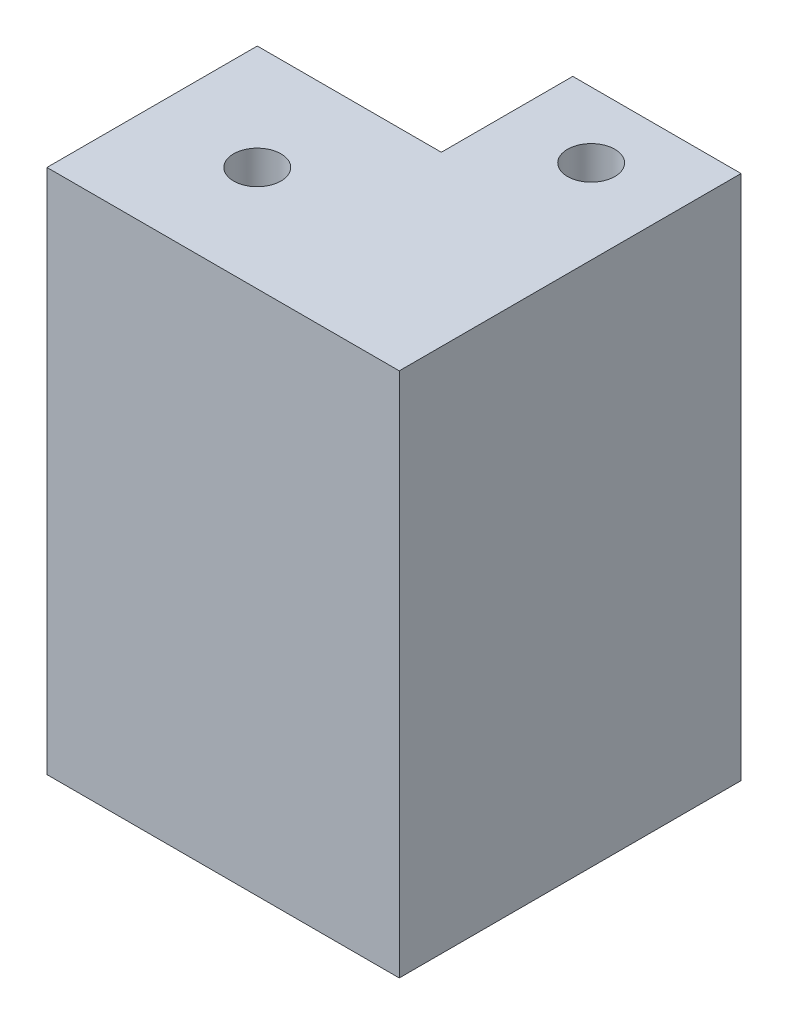
SolidWorks part; units mm, degrees
ref_plane "Front Plane" through (0, 0, 0) normal (0, 0, 1) x (1, 0, 0)
ref_plane "Top Plane" through (0, 0, 0) normal (0, 1, 0) x (1, 0, 0)
ref_plane "Right Plane" through (0, 0, 0) normal (1, 0, 0) x (0, 0, -1)
sketch "Sketch1" plane through (0, 0, 0) normal (0, 1, 0) x (1, 0, 0)
  line L19 (0, -40) -> (0, 0) construction
  line L24 (-25, 0) -> (-5, -40) construction
  line L25 (0, 25) -> (-25, 25) construction
  line L26 (-25, 25) -> (-25, 0) construction
  line L27 (0, 25) -> (32, 0) construction
  line L28 (32, 0) -> (0, 0) construction
  line L29 (-35, 0) -> (0, 0)
  line L30 (-35, -40) -> (-35, 0)
  line L31 (32, -40) -> (-35, -40)
  line L32 (32, 25) -> (32, -40)
  line L33 (0, 25) -> (32, 25)
  line L34 (0, 0) -> (0, 25)
  line L35 (-5, 5) -> (-5, -40) construction
  line L36 (-25, 25) -> (-5, 25) construction
  line L37 (-25, 25) -> (-25, 5) construction
  line L38 (-25, 5) -> (-5, 5) construction
  line L39 (-5, 25) -> (-5, 5) construction
  circle A10 centre (-15, -20) radius 16 construction
  circle A11 centre (-15, -20) radius 6.75 construction
  circle A12 centre (16, 12.5) radius 6 construction
  circle A13 centre (16, 12.5) radius 11 construction
  circle A14 centre (-15, -20) radius 4.5
  circle A15 centre (16, 12.5) radius 4.5
  point P1 (0, 0)
  dimension "D4" = 40
  dimension "D6" = 9
  dimension "D3" = 32
  dimension "D5" = 20
  dimension "D7" = 13.5
  dimension "D8" = 32
  dimension "D9" = 9
  dimension "D10" = 12
  dimension "D11" = 22
  dimension "D1" = 25
  dimension "D2" = 25
  dimension "D12" = 20
extrude "Boss-Extrude1" add sketch "Sketch1" along normal blind 100
sketch "Sketch4" plane through (0, 0, 0) normal (0, -1, 0) x (-1, 0, 0)
  point P0 (15, -20)
hole_wizard "CBORE for M5 Hex Head Bolt2" positions "Sketch4" profile "Sketch5" counterbore size "M5" standard "ANSI Metric"
sketch "Sketch5" plane through (-15, 0, 20) normal (1, 0, 0) x (0, 0, -1)
  line L0 (0, 0) -> (0, 23.85)
  line L1 (0, 23.85) -> (6.75, 23.85)
  line L2 (6.75, 23.85) -> (6.75, 5)
  line L3 (6.75, 5) -> (16, 5)
  line L4 (16, 5) -> (16, 0)
  line L5 (16, 0) -> (0, 0)
  line L10 (0, 23.85) -> (-6.75, 23.85) construction
  line L11 (0, -6.35) -> (0, 107.95) construction
  dimension "Hole Dia." = 13.5
  dimension "Hole Depth" = 23.85
  dimension "C'Bore Dia." = 32
  dimension "C'Bore Depth" = 5
  dimension "Drill Angle" = 180
sketch "Sketch6" plane through (0, 0, 0) normal (0, -1, 0) x (-1, 0, 0)
  point P0 (-16, 12.5)
hole_wizard "CBORE for M5 Hex Head Bolt3" positions "Sketch6" profile "Sketch7" counterbore size "M5" standard "ANSI Metric"
sketch "Sketch7" plane through (16, 0, -12.5) normal (1, 0, 0) x (0, 0, -1)
  line L0 (0, 0) -> (0, 13.5)
  line L1 (0, 13.5) -> (5.1, 13.5)
  line L2 (5.1, 13.5) -> (5.1, 3.5)
  line L3 (5.1, 3.5) -> (11, 3.5)
  line L4 (11, 3.5) -> (11, 0)
  line L5 (11, 0) -> (0, 0)
  line L10 (0, 13.5) -> (-5.1, 13.5) construction
  line L11 (0, -6.35) -> (0, 107.95) construction
  dimension "Hole Dia." = 10.2
  dimension "Hole Depth" = 13.5
  dimension "C'Bore Dia." = 22
  dimension "C'Bore Depth" = 3.5
  dimension "Drill Angle" = 180
